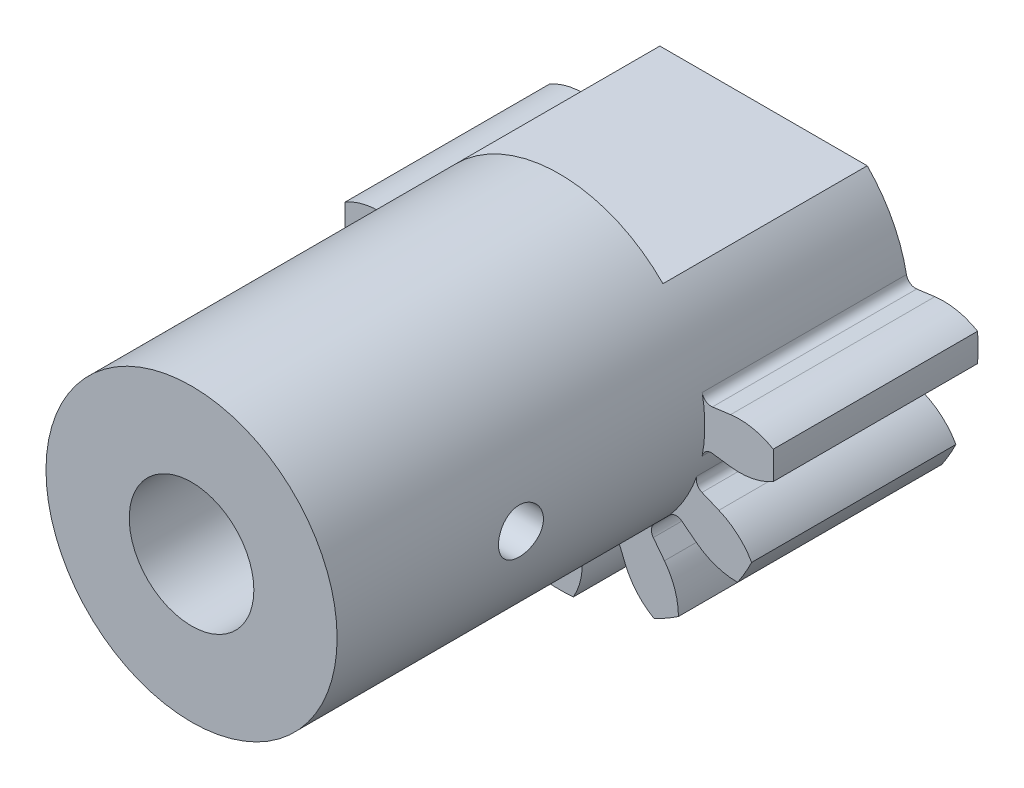
SolidWorks part; units mm, degrees
ref_plane "Front Plane" through (0, 0, 0) normal (0, 0, 1) x (1, 0, 0)
ref_plane "Top Plane" through (0, 0, 0) normal (0, 1, 0) x (1, 0, 0)
ref_plane "Right Plane" through (0, 0, 0) normal (1, 0, 0) x (0, 0, -1)
sketch "Esquisse1" plane through (0, 0, 0) normal (0, 0, 1) x (1, 0, 0)
  line L0 (0, 0) -> (22.1157, 0) construction
  line L1 (0, 0) -> (24.1492, 6.4708) construction
  line L2 (0, 0) -> (24.1492, -6.4708) construction
  line L3 (0, 0) -> (24.9429, 3.2838) construction
  line L4 (0, 0) -> (6.8822, 1.8441)
  line L5 (0, 0) -> (19.7164, -2.5957) construction
  line L6 (0, 0) -> (6.8822, -1.8441)
  line L7 (0, 0) -> (17.7915, 1.1661) construction
  line L8 (7.064, 0.93) -> (8.3849, 1.1039)
  line L9 (7.064, -0.93) -> (8.3849, -1.1039)
  line L10 (0, 0) -> (17.695, -1.1598) construction
  circle A0 centre (0, 0) radius 9 construction
  circle A1 centre (0, 0) radius 10.5 construction
  circle A2 centre (0, 0) radius 7.125 construction
  circle A3 centre (0, 0) radius 8.4572 construction
  arc A4 (6.8822, 1.8441) -> (7.064, 0.93) centre (0, 0) cw
  arc A5 (6.8822, -1.8441) -> (7.064, -0.93) centre (0, 0) ccw
  arc A6 (8.3849, 1.1039) -> (10.4775, 0.6867) centre (8.8176, -2.1828) cw
  arc A7 (10.4775, 0.6867) -> (10.4775, -0.6867) centre (0, 0) cw
  arc A8 (8.3849, -1.1039) -> (10.4775, -0.6867) centre (8.8176, 2.1828) ccw
  dimension "PrimitiveDiameter" = 18
  dimension "OutsideDiameter" = 21
  dimension "InternalDiameter" = 14.25
  dimension "BaseDiameter" = 16.9145
  dimension "DemiToothAngle" = 15
  dimension "QuartToothAngle" = 7.5
  dimension "D1" = 7.5
  dimension "D2" = 3.75
  dimension "D3" = 3.75
extrude "Boss.-Extru.2" add sketch "Esquisse1" along normal blind 10
fillet "Congé1" radius 0.45 2 edges at (7.064, -0.93, 5) (7.064, 0.93, 5)
ref_axis "Axe1" through (0, 0, 10) along (0, 0, -1)
pattern_circular "Répétition circulaire1" count 7 every 30 about axis through (0, 0, 10) along (0, 0, -1) of "Boss.-Extru.2", "Congé1"
sketch "Esquisse3" plane through (0, 0, 10) normal (0, 0, 1) x (1, 0, 0)
  circle A0 centre (0, 0) radius 1.6
  dimension "D1" = 3.2
sketch "Esquisse5" plane through (0, 0, 10) normal (0, 0, 1) x (1, 0, 0)
  circle A0 centre (0, 0) radius 7.125
  point P3 (0, 0)
extrude "Boss.-Extru.4" add sketch "Esquisse5" against normal through all
sketch "Esquisse7" plane through (0, 0, 10) normal (0, 0, 1) x (1, 0, 0)
  line L0 (-5.076, 5) -> (5.076, 5)
  circle A0 centre (0, 0) radius 7.125 construction
  arc A1 (5.076, 5) -> (-5.076, 5) centre (0, 0) ccw
  point P5 (0, 0)
  dimension "D1" = 5
extrude "Enlèv. mat.-Extru.3" cut sketch "Esquisse7" against normal through all
extrude "Enlèv. mat.-Extru.4" cut sketch "Esquisse3" against normal through all
sketch "Esquisse9" plane through (0, 0, 10) normal (0, 0, 1) x (1, 0, 0)
  circle A0 centre (0, 0) radius 7.125
  circle A1 centre (0, 0) radius 7.125 construction
  circle A2 centre (0, 0) radius 3.05
  dimension "D1" = 6.1
extrude "Boss.-Extru.5" add sketch "Esquisse9" along normal blind 18
sketch "Esquisse10" plane through (0, 0, 10) normal (0, 0, 1) x (1, 0, 0)
  line L0 (-3.05, 0) -> (3.05, 0)
  circle A0 centre (0, 0) radius 3.05 construction
  arc A1 (3.05, 0) -> (-3.05, 0) centre (0, 0) ccw
  circle A2 centre (0, 0) radius 3.05 construction
  point P6 (3.05, 0)
  point P8 (-3.1304, -0.5849)
  point P11 (-2.4299, -1.8433)
  point P12 (0, 0)
extrude "Boss.-Extru.6" add sketch "Esquisse10" along normal blind 5
sketch "Esquisse11" plane through (0, 0, 0) normal (1, 0, 0) x (0, -1, 0)
  line L0 (-7.125, -10) -> (7.125, -10) construction
  circle A0 centre (0, -19) radius 1.1
  point P4 (0, 0)
  dimension "D1" = 2.2
  dimension "D2" = 9
extrude "Enlèv. mat.-Extru.6" cut sketch "Esquisse11" against normal through all both and the other way through all
equation "\"Modulo\"= 1.5mm"
equation "\"ToothCount\"= 12"
equation "\"PrimitiveDiameter@Esquisse1\"= \"Modulo\" * \"ToothCount\""
equation "\"OutsideDiameter@Esquisse1\" = \"Modulo\" *  ( \"ToothCount\" + 2 ) "
equation "\"InternalDiameter@Esquisse1\" = \"PrimitiveDiameter@Esquisse1\" - \"Modulo\" * 2.5"
equation "\"Angle\"= 20deg"
equation "\"BaseDiameter@Esquisse1\" = \"PrimitiveDiameter@Esquisse1\" * cos ( \"Angle\" ) "
equation "\"DemiToothAngle@Esquisse1\" = 180 / \"ToothCount\""
equation "\"QuartToothAngle@Esquisse1\"= \"DemiToothAngle@Esquisse1\" / 2"
equation "\"D1@Esquisse1\"= \"QuartToothAngle@Esquisse1\""
equation "\"D2@Esquisse1\"= \"QuartToothAngle@Esquisse1\" / 2"
equation "\"D3@Esquisse1\"= \"D2@Esquisse1\""
equation "\"D2@Répétition circulaire1\"=360/\"ToothCount\""
equation "\"D1@Congé1\"=\"Modulo\"*0.3"
